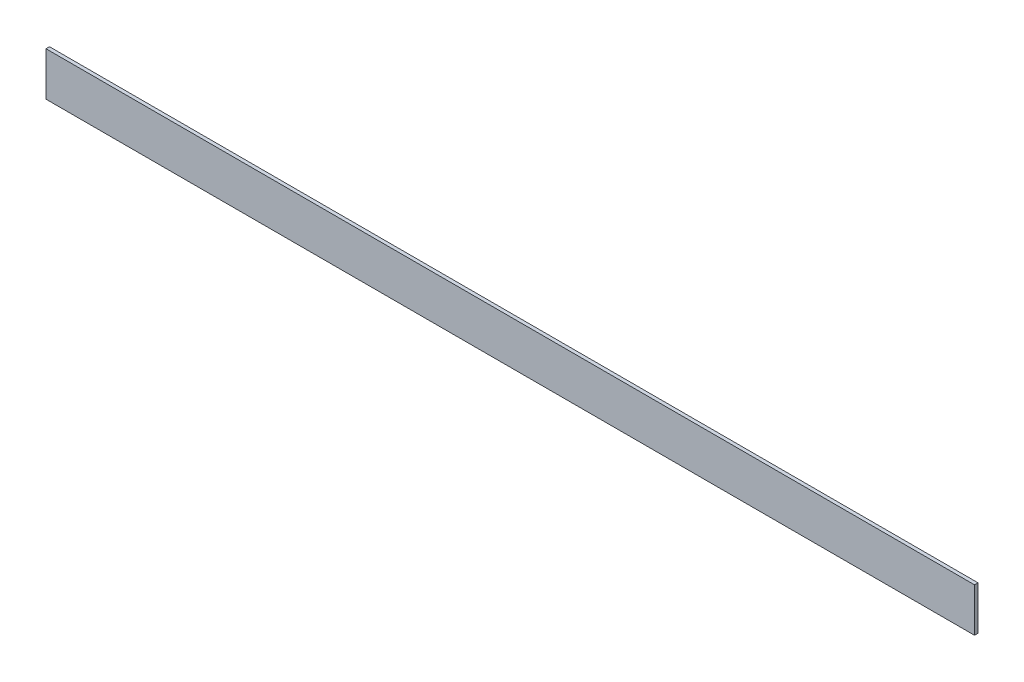
SolidWorks part; units mm, degrees
ref_plane "Спереди" through (0, 0, 0) normal (0, 0, 1) x (1, 0, 0)
ref_plane "Сверху" through (0, 0, 0) normal (0, 1, 0) x (1, 0, 0)
ref_plane "Справа" through (0, 0, 0) normal (1, 0, 0) x (0, 0, -1)
sketch "Эскиз1" plane through (0, 0, 0) normal (1, 0, 0) x (0, 0, -1)
  line L0 (0, 25) -> (0, 0)
  line L1 (0, 0) -> (25, 0)
extrude "Вытянуть-Тонкостенный1" add sketch "Эскиз1" along normal blind 531 thin thin type one direction reverse wall 2
sketch "Эскиз2" plane through (0, 0, 0) normal (0, -1, 0) x (1, 0, 0)
  line L0 (531, -25) -> (0, -25) construction
  line L1 (0, -2) -> (23, -2)
  line L2 (0, -2) -> (0, -25)
  line L3 (0, -25) -> (23, -25)
  line L4 (23, -2) -> (23, -25)
  line L6 (265.5, -54.7681) -> (265.5, 4.7681) construction
  line L7 (508, -2) -> (508, -25)
  line L8 (531, -25) -> (508, -25)
  line L9 (531, -2) -> (531, -25)
  line L10 (531, -2) -> (508, -2)
  point P4 (265.5, -25)
  dimension "D1" = 23
extrude "Вырез-Вытянуть1" cut sketch "Эскиз2" against normal through all
